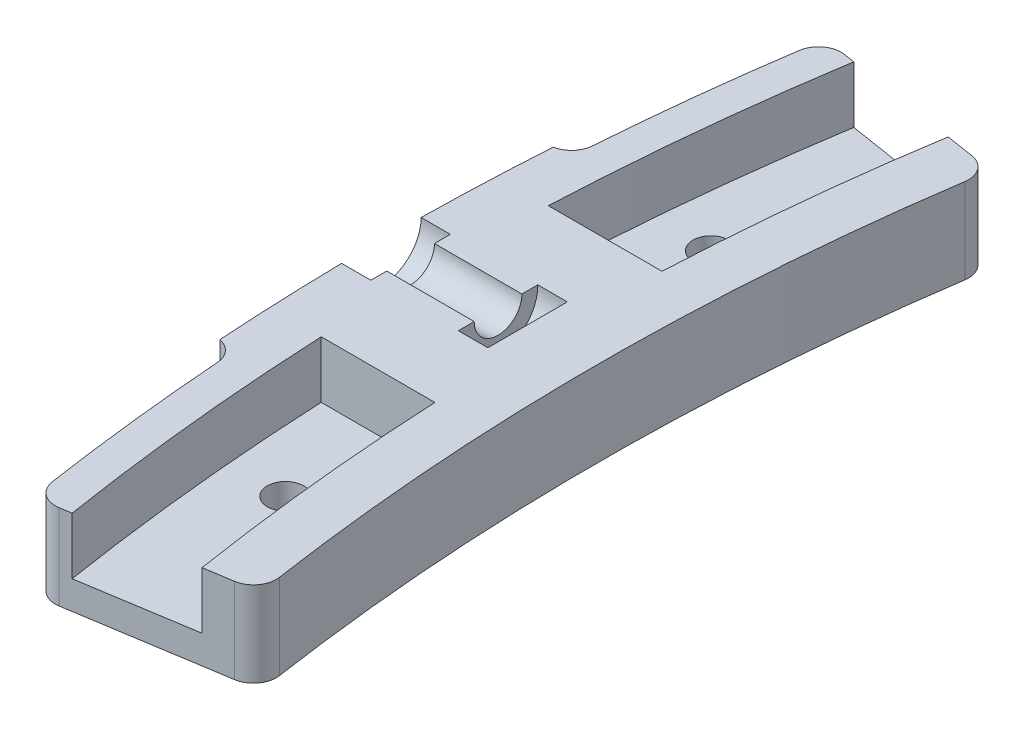
SolidWorks part; units mm, degrees
ref_plane "Front Plane" through (0, 0, 0) normal (0, 0, 1) x (1, 0, 0)
ref_plane "Top Plane" through (0, 0, 0) normal (0, 1, 0) x (1, 0, 0)
ref_plane "Right Plane" through (0, 0, 0) normal (1, 0, 0) x (0, 0, -1)
sketch "Sketch1" plane through (0, 0, 0) normal (0, 1, 0) x (1, 0, 0)
  line L0 (0, 0) -> (-217.2914, -34.4156) construction
  line L1 (0, 0) -> (-217.2914, 34.4156) construction
  line L2 (0, 0) -> (-215, 0) construction
  line L3 (-217.2914, 34.4156) -> (-207.4146, 32.8512)
  line L4 (-207.4146, -32.8512) -> (-217.2914, -34.4156)
  line L5 (0, 0) -> (-220.2545, -34.8849) construction
  line L6 (0, 0) -> (-220.2545, 34.8849) construction
  line L7 (-220.2545, 34.8849) -> (-202.97, 32.1473)
  line L8 (-220.2545, -34.8849) -> (-202.97, -32.1473)
  arc A0 (-217.2914, 34.4156) -> (-217.2914, -34.4156) centre (0, 0) ccw
  arc A1 (-207.4146, 32.8512) -> (-207.4146, -32.8512) centre (0, 0) ccw
  arc A2 (-212.353, -33.6334) -> (-212.353, 33.6334) centre (0, 0) cw construction
  arc A4 (-202.97, 32.1473) -> (-202.97, -32.1473) centre (0, 0) ccw
  arc A5 (-220.2545, 34.8849) -> (-220.2545, -34.8849) centre (0, 0) ccw
  dimension "D1" = 220
  dimension "D2" = 210
  dimension "D3" = 5
  dimension "D5" = 205.5
  dimension "D6" = 223
  dimension "D4" = 18
extrude "Boss-Extrude1" add sketch "Sketch1" along normal blind 7.5 contours A1 L3 A0 L4 | L7 A5 L8 A0 | A4 L7 A1 L8
ref_plane "Plane1" through (-215, 0, 0) normal (1, 0, 0) x (0, 0, -1)
sketch "Sketch19" plane through (0, 0, 0) normal (0, 1, 0) x (1, 0, 0)
  line L0 (0, 0) -> (-224.0193, 14.683) construction
  line L1 (0, 0) -> (-224.0193, -14.683) construction
  line L4 (0, 0) -> (-224.5, 0) construction
  line L5 (-224.0193, 14.683) -> (-222.5225, 14.5849)
  line L6 (-224.0193, -14.683) -> (-222.5225, -14.5849)
  arc A0 (-224.0193, 14.683) -> (-224.0193, -14.683) centre (0, 0) ccw
  arc A1 (-220.2545, 34.8849) -> (-220.2545, -34.8849) centre (0, 0) ccw construction
  arc A2 (-222.5225, 14.5849) -> (-222.5225, -14.5849) centre (0, 0) ccw
  dimension "D1" = 224.5
  dimension "D2" = 3.75
extrude "Boss-Extrude2" add sketch "Sketch19" along normal blind 7.5
sketch "Sketch15" plane through (0, 7.5, 0) normal (0, 1, 0) x (1, 0, 0)
  line L0 (-207.4146, -32.8512) -> (-217.2914, -34.4156) construction
  line L1 (-205, 10) -> (-225, 10)
  line L2 (-205, 10) -> (-205, -10)
  line L3 (-205, -10) -> (-225, -10)
  line L4 (-225, 10) -> (-225, -10)
  line L5 (-205, 10) -> (-225, -10) construction
  line L6 (-205, -10) -> (-225, 10) construction
  line L7 (-217.2914, 34.4156) -> (-207.4146, 32.8512) construction
  line L8 (-207.4146, -32.8512) -> (-217.2914, -34.4156)
  line L9 (-217.2914, 34.4156) -> (-207.4146, 32.8512)
  arc A2 (-207.4146, 32.8512) -> (-207.4146, -32.8512) centre (0, 0) ccw construction
  arc A3 (-217.2914, 34.4156) -> (-217.2914, -34.4156) centre (0, 0) ccw construction
  arc A4 (-207.4146, 32.8512) -> (-207.4146, -32.8512) centre (0, 0) ccw
  arc A5 (-217.2914, 34.4156) -> (-217.2914, -34.4156) centre (0, 0) ccw
  point P0 (-215, 0)
  line M5 (-220.2545, -34.8849) -> (-202.97, -32.1473)
  line M7 (-202.97, 32.1473) -> (-220.2545, 34.8849)
  dimension "D1" = 20
  dimension "D2" = 20
extrude "Cut-Extrude1" cut sketch "Sketch15" against normal blind 5 contours A5 L1 A4 M7 | L3 A5 A4 M5
ref_plane "Plane2" through (-215, 0, 0) normal (-1, 0, 0) x (0, 0, 1)
sketch "Sketch12" plane through (0, 0, 0) normal (0, 1, 0) x (1, 0, 0)
  line L0 (0, 0) -> (-214.1819, -18.7385) construction
  line L1 (0, 0) -> (-213.1606, -28.0631) construction
  line L2 (0, 0) -> (-215, 0) construction
  line L3 (0, 0) -> (-215, 0) construction
  line L4 (0, 0) -> (-214.1819, 18.7385) construction
  line L5 (0, 0) -> (-213.1606, 28.0631) construction
  arc A0 (-212.353, 33.6334) -> (-212.353, -33.6334) centre (0, 0) ccw construction
  dimension "D1" = 10
  dimension "D2" = 15
hole_wizard "Ø3.2 (3.2) Diameter Hole1" positions "Sketch18" profile "Sketch17" hole size "Ø3.2" standard "ISO" end condition through all
sketch "Sketch18" plane through (0, 0, 0) normal (0, -1, 0) x (-1, 0, 0)
  point P3 (214.1819, -18.7385)
  point P6 (214.1819, 18.7385)
sketch "Sketch17" plane through (-214.1819, 0, 18.7385) normal (1, 0, 0) x (0, 0, -1)
  line L0 (0, 0) -> (0, 7.5)
  line L1 (0, 7.5) -> (1.6, 7.5)
  line L2 (1.6, 7.5) -> (1.6, 0)
  line L5 (1.6, 0) -> (0, 0)
  line L11 (0, -6.35) -> (0, 107.95) construction
  dimension "Thru Hole Dia." = 3.2
  dimension "Thru Hole Depth" = 7.5
sketch "Sketch20" plane through (0, 0, 0) normal (0, 1, 0) x (1, 0, 0)
  line L0 (-205, 0) -> (-192.5, 0) construction
  line L1 (0, 0) -> (-205, 0) construction
  arc A2 (-224.0193, 14.683) -> (-224.0193, -14.683) centre (0, 0) ccw construction
  point P3 (-224.5, 0)
  dimension "D1" = 205
  dimension "D2" = 12.5
ref_plane "Plane3" through (-192.5, 0, 0) normal (1, 0, 0) x (0, 0, -1)
ref_plane "Plane4" through (-224.5, 0, 0) normal (1, 0, 0) x (0, 0, -1)
fillet "Fillet1" radius 2 4 edges at (-220.2545, 3.75, -34.8849) (-202.97, 3.75, -32.1473) (-202.97, 3.75, 32.1473) (-220.2545, 3.75, 34.8849)
fillet "Fillet2" radius 2 2 edges at (-222.5225, 3.75, -14.5849) (-222.5225, 3.75, 14.5849)
sketch "Sketch21" plane through (0, 7.5, 0) normal (0, 1, 0) x (1, 0, 0)
  line L0 (-225, 0) -> (0, 0) construction
  line L1 (-225, 0) -> (-212.5, 0) construction
  dimension "D1" = 225
  dimension "D2" = 12.5
ref_plane "Plane5" through (-212.5, 0, 0) normal (1, 0, 0) x (0, 0, -1)
sketch "Sketch22" plane through (-212.5, 0, 0) normal (1, 0, 0) x (0, 0, -1)
  line L0 (30.1895, 7.5) -> (-30.1895, 7.5) construction
  circle A0 centre (0, 7.5) radius 2.1
  dimension "D1" = 4.2
extrude "Cut-Extrude2" cut sketch "Sketch22" against normal through all and the other way up to surface (0.9 mm away)
sketch "Sketch23" plane through (-211.6, 0, 0) normal (-1, 0, 0) x (0, 0, 1)
  circle A0 centre (0, 7.4392) radius 3.5
  dimension "D1" = 7
extrude "Cut-Extrude3" cut sketch "Sketch23" along normal blind 2.6
sketch "Sketch24" plane through (0, 7.5, 0) normal (0, 1, 0) x (1, 0, 0)
  line L0 (-224.5, 0) -> (-205.5, 0) construction
  line L2 (-224.5, 0) -> (-221.9, 0)
  line L3 (-224.5, 0) -> (-224.5, 3.5)
  line L4 (-224.5, 3.5) -> (-221.9, 3.5)
  line L5 (-221.9, 0) -> (-221.9, 3.5)
  arc A0 (-224.4902, 2.1) -> (-224.4902, -2.1) centre (0, 0) ccw construction
  arc A1 (-203.2704, 30.1895) -> (-203.2704, -30.1895) centre (0, 0) ccw construction
  dimension "D1" = 2.6
  dimension "D2" = 7
revolve "Cut-Revolve1" cut sketch "Sketch24" angle 360 about L0
